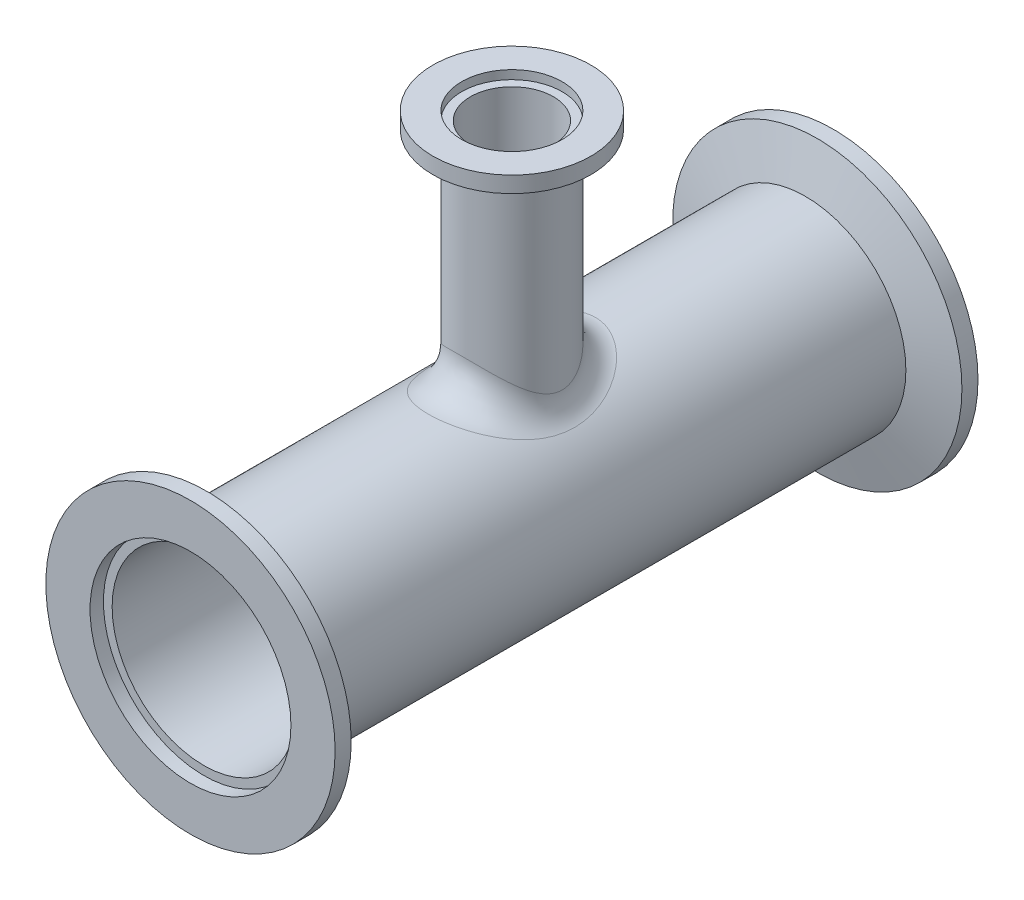
SolidWorks part; units mm, degrees
ref_plane "Front" through (0, 0, 0) normal (0, 0, 1) x (1, 0, 0)
ref_plane "Top" through (0, 0, 0) normal (0, 1, 0) x (1, 0, 0)
ref_plane "Right" through (0, 0, 0) normal (1, 0, 0) x (0, 0, -1)
sketch "Sketch1" plane through (0, 0, 0) normal (1, 0, 0) x (0, 0, -1)
  line L0 (-60.96, 0) -> (60.96, 0) construction
  line L1 (60.96, 27.432) -> (60.96, 19.05)
  line L2 (60.96, 19.05) -> (58.42, 19.05)
  line L3 (58.42, 19.05) -> (58.42, 17.399)
  line L4 (58.42, 17.399) -> (-60.96, 17.399) construction
  line L5 (-60.96, 17.399) -> (-60.96, 19.05) construction
  line L6 (-60.96, 19.05) -> (55.666, 19.05) construction
  line L7 (55.666, 19.05) -> (57.912, 27.432)
  line L8 (57.912, 27.432) -> (60.96, 27.432)
  line L9 (58.42, 17.399) -> (-58.42, 17.399)
  line L10 (-58.42, 17.399) -> (-58.42, 19.05)
  line L11 (-58.42, 19.05) -> (-60.96, 19.05)
  line L12 (-60.96, 19.05) -> (-60.96, 27.432)
  line L13 (-60.96, 27.432) -> (-57.912, 27.432)
  line L14 (-57.912, 27.432) -> (-55.666, 19.05)
  line L15 (-55.666, 19.05) -> (55.666, 19.05)
  dimension "D1" = 15
  dimension "Th" = 1.651
  dimension "D3" = 3.048
  dimension "D4" = 2.54
  dimension "Length" = 121.92
  dimension "Flange OD" = 54.864
  dimension "Edge" = 38.1
revolve "Revolve1" add sketch "Sketch1" angle 360 about L0
sketch "Sketch2" plane through (0, 0, 0) normal (1, 0, 0) x (0, 0, -1)
  line L0 (0, 60.96) -> (0, -60.96) construction
  line L2 (-9.525, 60.96) -> (-14.986, 60.96)
  line L3 (-14.986, 60.96) -> (-14.986, 57.912)
  line L4 (-14.986, 57.912) -> (-9.525, 56.9491)
  line L12 (-7.874, 59.309) -> (-9.525, 59.309)
  line L13 (-9.525, 59.309) -> (-9.525, 60.96)
  line L15 (-60.96, 27.432) -> (-57.912, 27.432) construction
  line L18 (-55.666, 17.399) -> (-55.666, 19.05) construction
  line L19 (-7.874, 59.309) -> (-7.874, 0)
  line L20 (-58.42, 17.399) -> (-58.42, 19.05) construction
  line L21 (-7.874, 0) -> (-9.525, 0)
  line L22 (-9.525, 0) -> (-9.525, 56.9491)
  line L23 (58.42, 17.399) -> (-58.42, 17.399) construction
  line L24 (-55.666, 19.05) -> (-55.666, -19.05) construction
  dimension "D1" = 29.972
  dimension "D2" = 100
  dimension "A" = 60.96
  dimension "B Tube OD" = 19.05
revolve "Revolve2" add sketch "Sketch2" angle 360 about L0
sketch "Sketch3" plane through (0, 0, -60.96) normal (0, 0, -1) x (-1, 0, 0)
  circle A0 centre (0, 0) radius 17.399
  circle A1 centre (0, 0) radius 17.399 construction
extrude "Cut-Extrude1" cut sketch "Sketch3" against normal through all
sketch "Sketch4" plane through (0, 60.96, 0) normal (0, 1, 0) x (-1, 0, 0)
  circle A0 centre (0, 0) radius 7.874
  circle A2 centre (0, 0) radius 7.874 construction
extrude "Cut-Extrude2" cut sketch "Sketch4" against normal up to surface (43.561 mm away) up to face at (17.399, 0, 58.42)
fillet "Fillet1" radius 6.35 2 edges at (0.9668, 17.3721, -7.8144) (0.9612, 19.0257, -9.4764)
